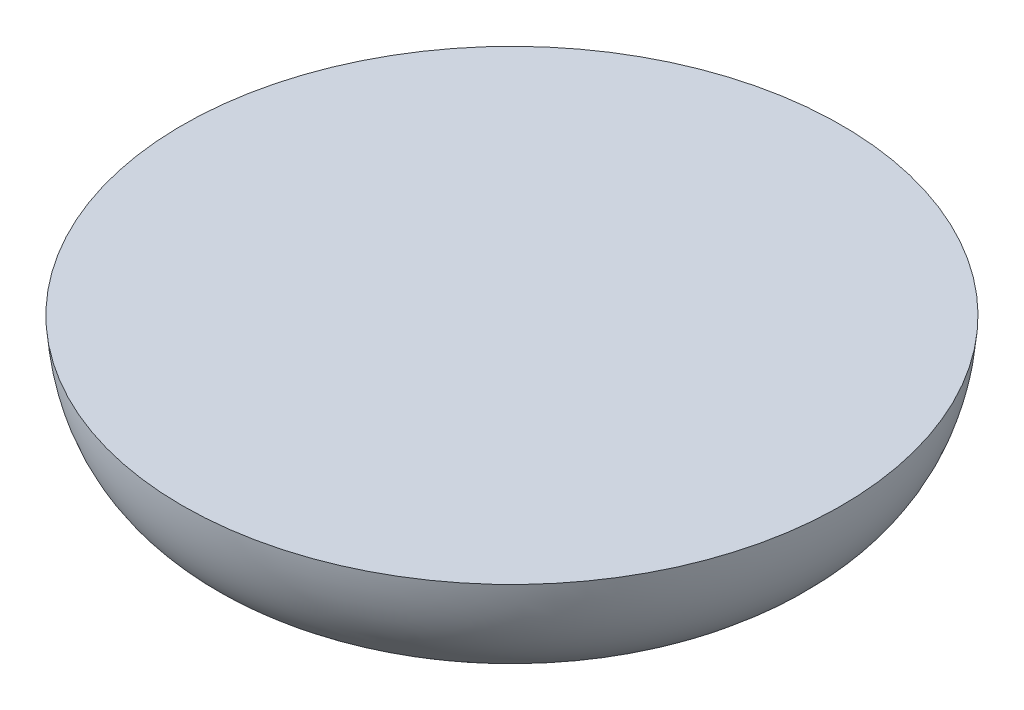
SolidWorks part; units mm, degrees
ref_plane "Front Plane" through (0, 0, 0) normal (0, 0, 1) x (1, 0, 0)
ref_plane "Top Plane" through (0, 0, 0) normal (0, 1, 0) x (1, 0, 0)
ref_plane "Right Plane" through (0, 0, 0) normal (1, 0, 0) x (0, 0, -1)
ref_axis "Axis1" through (-33.0333, 0, 0) along (1, 0, 0)
ref_axis "Axis2" through (0, 24.5224, 0) along (0, -1, 0)
ref_axis "Axis3" through (0, 0, -30.7663) along (0, 0, 1)
sketch "Sketch1" plane through (0, 0, 0) normal (0, 0, 1) x (1, 0, 0)
  line L17 (-8.5, -4.1129) -> (-13.4915, -4.1129)
  line L22 (-24.1, 5.2071) -> (0, 5.2071)
  line L28 (0, 5.2071) -> (0, -5.7929)
  line L29 (0, -5.7929) -> (-8.5, -5.7929)
  line L30 (-8.5, -5.7929) -> (-8.5, -4.1129)
  spline S1 degree 2 poles (-24.1, 5.2071) (-23.4032, -4.3148) (-13.4915, -4.1129) knots 0 0 0 1 1 1
  dimension "D2" = 11
  dimension "D1" = 24.1
  dimension "D3" = 8.5
  dimension "D4" = 1.68
  dimension "D5" = 13.4915
revolve "Revolve1" add sketch "Sketch1" angle 360 about axis through (0, 24.5224, 0) along (0, -1, 0)
scale "Scale1" scale about centroid uniform scaling yes scale factor 1.05
